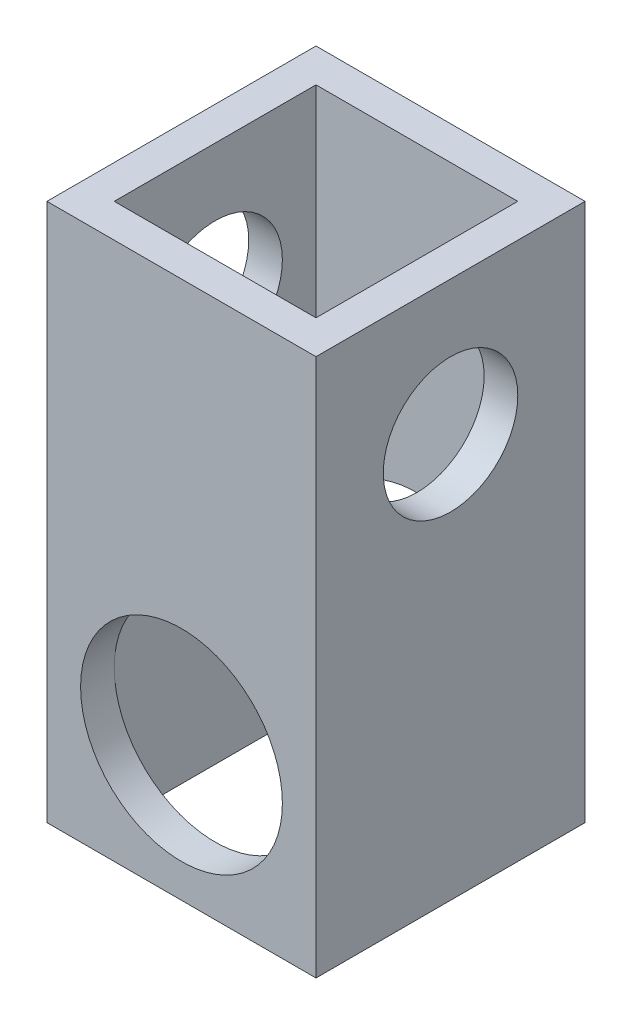
SolidWorks part; units mm, degrees
material "1060 Alloy"
ref_plane "Front Plane" through (0, 0, 0) normal (0, 0, 1) x (1, 0, 0)
ref_plane "Top Plane" through (0, 0, 0) normal (0, 1, 0) x (1, 0, 0)
ref_plane "Right Plane" through (0, 0, 0) normal (1, 0, 0) x (0, 0, -1)
sketch "Sketch1" plane through (0, 0, 0) normal (0, 1, 0) x (1, 0, 0)
  line L1 (-12.7, -12.7) -> (12.7, -12.7)
  line L2 (-12.7, -12.7) -> (-12.7, 12.7)
  line L3 (-12.7, 12.7) -> (12.7, 12.7)
  line L4 (12.7, -12.7) -> (12.7, 12.7)
  line L5 (-12.7, -12.7) -> (12.7, 12.7) construction
  line L6 (-12.7, 12.7) -> (12.7, -12.7) construction
  point P0 (0, 0)
  dimension "D1" = 25.4
extrude "Extrude-Thin1" add sketch "Sketch1" along normal blind 50.8 thin thin type one direction reverse wall 3.175
sketch "Sketch2" plane through (12.7, 0, 0) normal (1, 0, 0) x (0, 0, -1)
  line L0 (-12.7, 50.8) -> (12.7, 50.8) construction
  circle A0 centre (0, 38.1) radius 6.35
  point P5 (0, 50.8)
  dimension "D1" = 12.7
  dimension "D2" = 12.7
extrude "Cut-Extrude1" cut sketch "Sketch2" against normal through all
sketch "Sketch3" plane through (0, 0, -12.7) normal (0, 0, -1) x (-1, 0, 0)
  line L0 (-12.7, 0) -> (12.7, 0) construction
  circle A0 centre (0, 12.7) radius 9.525
  dimension "D1" = 19.05
  dimension "D2" = 12.7
extrude "Cut-Extrude2" cut sketch "Sketch3" against normal through all
sketch "Sketch4" [suppressed] plane through (12.7, 0, 0) normal (1, 0, 0) x (0, 0, -1)
  line L0 (-12.7, 203.2) -> (12.7, 203.2) construction
  line L1 (-12.7, 203.2) -> (-12.7, 0) construction
  line L2 (0, 190.5) -> (-12.7, 190.5) construction
  line L3 (-12.7, 190.5) -> (-12.7, 203.2)
  line L4 (-12.7, 203.2) -> (0, 203.2)
  arc A0 (0, 203.2) -> (-12.7, 190.5) centre (0, 190.5) ccw
extrude "Cut-Extrude3" [suppressed] cut sketch "Sketch4" against normal through all
